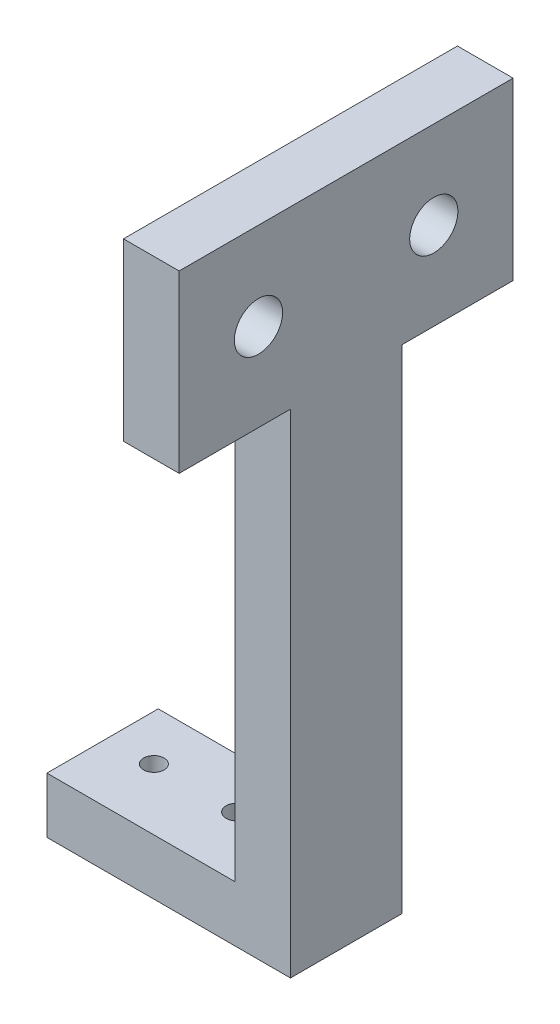
SolidWorks part; units mm, degrees
material "PLA Yellow"
ref_plane "Front Plane" through (0, 0, 0) normal (0, 0, 1) x (1, 0, 0)
ref_plane "Top Plane" through (0, 0, 0) normal (0, 1, 0) x (1, 0, 0)
ref_plane "Right Plane" through (0, 0, 0) normal (1, 0, 0) x (0, 0, -1)
sketch "Sketch1" plane through (0, 0, 0) normal (0, 0, 1) x (1, 0, 0)
  line L0 (-13.8933, 0) -> (13.8933, 0)
  line L10 (13.8933, 76.2) -> (7.5433, 76.2)
  line L11 (7.5433, 76.2) -> (7.5433, 6.35)
  line L12 (7.5433, 6.35) -> (-13.8933, 6.35)
  line L13 (-13.8933, 6.35) -> (-13.8933, 0)
  line L14 (13.8933, 76.2) -> (13.8933, 0)
  point P6 (0, 0)
  dimension "D1" = 27.7866
  dimension "D2" = 76.2
  dimension "D3" = 6.35
  dimension "D4" = 6.35
extrude "Boss-Extrude1" add sketch "Sketch1" along normal mid plane 12.7
sketch "Sketch2" plane through (7.5433, 0, 0) normal (-1, 0, 0) x (0, 0, 1)
  line L0 (6.35, 76.2) -> (-6.35, 76.2) construction
  line L1 (-19.05, 56.2) -> (19.05, 56.2)
  line L2 (-19.05, 56.2) -> (-19.05, 76.2)
  line L3 (-19.05, 76.2) -> (19.05, 76.2)
  line L4 (19.05, 56.2) -> (19.05, 76.2)
  line L5 (-19.05, 56.2) -> (19.05, 76.2) construction
  line L6 (-19.05, 76.2) -> (19.05, 56.2) construction
  point P0 (0, 66.2)
  point P5 (0, 76.2)
  point P8 (0, 76.2)
  dimension "D1" = 20
  dimension "D2" = 38.1
extrude "Boss-Extrude2" add sketch "Sketch2" against normal up to surface (6.35 mm away) up to face at (13.8933, 38.1, 0)
sketch "Sketch3" plane through (0, 6.35, 0) normal (0, 1, 0) x (1, 0, 0)
  arc A0 (0.3802, 1.825) -> (0.3802, -0.525) centre (0.8067, 0.65) ccw construction
  circle A1 centre (-8.6933, 0.65) radius 1.175 construction
  arc A2 (0.3802, 1.825) -> (0.3802, -0.525) centre (0.8067, 0.65) ccw
  circle A3 centre (-8.6933, 0.65) radius 1.175
  circle A4 centre (0.8067, 0.65) radius 1.25
extrude "Cut-Extrude1" cut sketch "Sketch3" against normal through all contours A2 A4 | A3 region at (0.8067, 6.35, -0.65) region at (-8.6933, 6.35, -0.65)
sketch "Sketch4" plane through (7.5433, 0, 0) normal (-1, 0, 0) x (0, 0, 1)
  line L0 (-10, 66.2) -> (10, 66.2) construction
  line L1 (-19.05, 56.2) -> (19.05, 76.2) construction
  circle A0 centre (-10, 66.2) radius 2.75
  circle A1 centre (10, 66.2) radius 2.75
  point P6 (0, 66.2)
  point P9 (0, 66.2)
  dimension "D1" = 5.5
  dimension "D2" = 20
extrude "Cut-Extrude2" cut sketch "Sketch4" against normal through all
